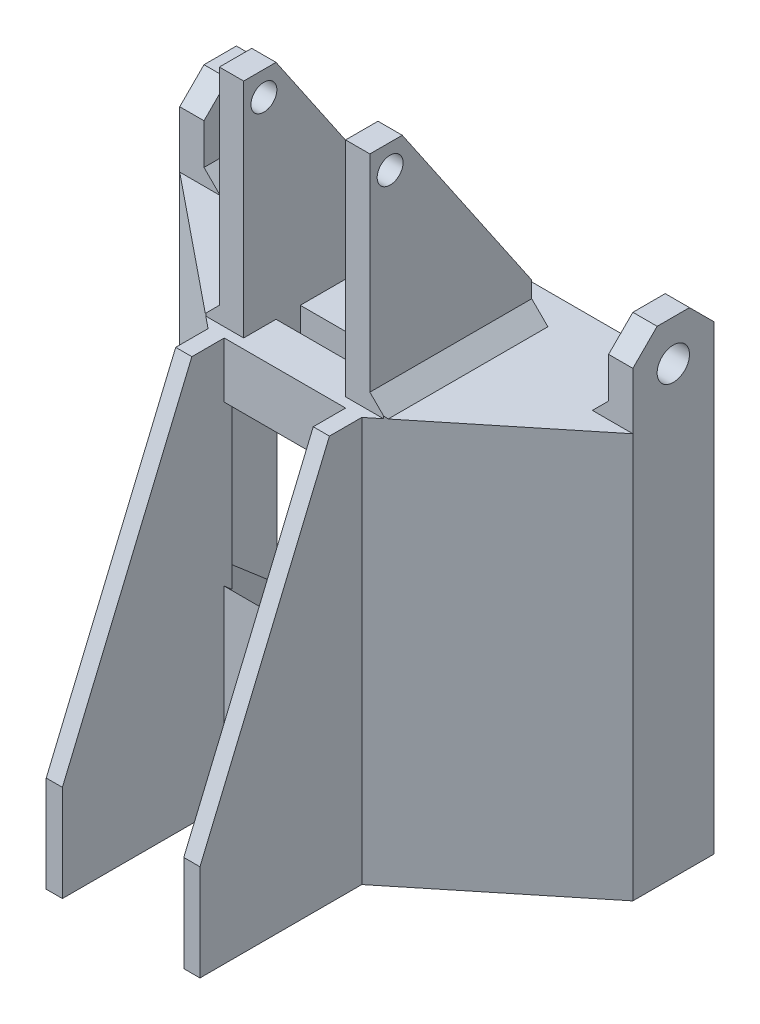
SolidWorks part; units mm, degrees
ref_plane "Alzado" through (0, 0, 0) normal (0, 0, 1) x (1, 0, 0)
ref_plane "Planta" through (0, 0, 0) normal (0, 1, 0) x (1, 0, 0)
ref_plane "Vista lateral" through (0, 0, 0) normal (1, 0, 0) x (0, 0, -1)
sketch "Croquis1" plane through (0, 0, 0) normal (0, 1, 0) x (1, 0, 0)
  line L0 (-26, 17.3913) -> (-26, 8.3445)
  line L1 (-26, 8.3445) -> (-7.5, -6.6555)
  line L2 (-7.5, -6.6555) -> (-7.5, -32.6087)
  line L3 (-7.5, -32.6087) -> (-9.5, -32.6087)
  line L4 (-9.5, -32.6087) -> (-9.5, -7.6087)
  line L5 (-9.5, -7.6087) -> (-28, 7.3913)
  line L6 (-28, 7.3913) -> (-28, 17.3913)
  line L7 (-28, 17.3913) -> (-26, 17.3913)
  line L16 (7.5, -6.6555) -> (7.5, -32.6087)
  line L17 (7.5, -32.6087) -> (9.5, -32.6087)
  line L18 (9.5, -32.6087) -> (9.5, -7.6087)
  line L19 (9.5, -7.6087) -> (28, 7.3913)
  line L20 (28, 7.3913) -> (28, 17.3913)
  line L21 (28, 17.3913) -> (26, 17.3913)
  line L22 (26, 17.3913) -> (26, 8.3445)
  line L23 (26, 8.3445) -> (7.5, -6.6555)
  line L24 (-26, 17.3913) -> (26, 17.3913) construction
  line L25 (-7.5, -32.6087) -> (7.5, -32.6087) construction
  point P10 (0, -32.6087)
  point P17 (0, 17.3913)
  dimension "D1" = 52
  dimension "D2" = 15
  dimension "D3" = 2
  dimension "D4" = 2
  dimension "D5" = 2
  dimension "D6" = 15
  dimension "D7" = 25
  dimension "D8" = 10
extrude "Saliente-Extruir1" add sketch "Croquis1" along normal blind 45
sketch "Croquis2" plane through (0, 45, 0) normal (0, 1, 0) x (1, 0, 0)
  line L0 (-9.5, -32.6087) -> (9.5, -32.6087)
  line L1 (9.5, -32.6087) -> (9.5, -7.6087)
  line L2 (9.5, -7.6087) -> (28, 7.3913)
  line L3 (28, 7.3913) -> (28, 17.3913)
  line L4 (28, 17.3913) -> (-28, 17.3913)
  line L5 (-28, 17.3913) -> (-28, 7.3913)
  line L6 (-28, 7.3913) -> (-9.5, -7.6087)
  line L7 (-9.5, -7.6087) -> (-9.5, -32.6087)
extrude "Saliente-Extruir2" add sketch "Croquis2" along normal blind 3
extrude "Saliente-Extruir3" add sketch "Croquis2<2>" against normal blind 2 from surface starting at face at (-17.75, 0, 3.6204)
sketch "Croquis2<2>" plane through (0, 45, 0) normal (0, 1, 0) x (1, 0, 0) same geometry as "Croquis2"
sketch "Croquis4" plane through (0, 48, 0) normal (0, 1, 0) x (1, 0, 0)
  line L1 (-28, 17.3913) -> (-25, 17.3913)
  line L2 (-28, 17.3913) -> (-28, 7.3913)
  line L3 (-28, 7.3913) -> (-25, 7.3913)
  line L4 (-25, 17.3913) -> (-25, 7.3913)
  line L5 (28, 17.3913) -> (25, 17.3913)
  line L6 (28, 17.3913) -> (28, 7.3913)
  line L7 (28, 7.3913) -> (25, 7.3913)
  line L8 (25, 17.3913) -> (25, 7.3913)
  dimension "D1" = 3
  dimension "D2" = 3
extrude "Saliente-Extruir4" add sketch "Croquis4" along normal blind 10
sketch "Croquis5" plane through (28, 0, 0) normal (1, 0, 0) x (0, 0, -1)
  line L0 (7.3913, 58) -> (17.3913, 58) construction
  circle A0 centre (12.3913, 53) radius 2
  dimension "D1" = 4
  dimension "D2" = 5
extrude "Cortar-Extruir1" cut sketch "Croquis5" against normal through all
chamfer "Chaflán1" distance 3 angle 45 4 edges at (-26.5, 58, -7.3913) (-26.5, 58, -17.3913) (26.5, 58, -7.3913) (26.5, 58, -17.3913)
sketch "Croquis7" plane through (9.5, 0, 0) normal (1, 0, 0) x (0, 0, -1)
  line L0 (-32.6087, -2) -> (-11.6087, 48)
  line L1 (-32.6087, 48) -> (-7.6087, 48) construction
  line L2 (-11.6087, 48) -> (-32.6087, 48)
  line L3 (-32.6087, 48) -> (-32.6087, -2)
  dimension "D1" = 4
extrude "Cortar-Extruir3" cut sketch "Croquis7" against normal through all
sketch "Croquis13" plane through (-26, 0, 0) normal (1, 0, 0) x (0, 0, -1)
  line L0 (17.3913, 45) -> (-12.8687, 45)
  line L1 (-12.8687, 45) -> (-14.9687, 40)
  line L2 (-32.6087, -2) -> (-11.6087, 48) construction
  line L3 (-14.9687, 40) -> (17.3913, 45)
  line L4 (17.3913, 0) -> (-31.7687, 0)
  line L5 (-32.6087, -2) -> (-11.6087, 48) construction
  line L6 (-31.7687, 0) -> (-18.7487, 31)
  line L7 (-18.7487, 31) -> (17.3913, 0)
  dimension "D1" = 5
  dimension "D2" = 9
extrude "Saliente-Extruir7" add sketch "Croquis13" along normal through all
sketch "Croquis6" plane through (0, -2, 0) normal (0, -1, 0) x (1, 0, 0)
  line L1 (-7.5, 27.6087) -> (7.5, 27.6087)
  line L2 (-7.5, 27.6087) -> (-7.5, 7.6087)
  line L3 (-7.5, 7.6087) -> (7.5, 7.6087)
  line L4 (7.5, 27.6087) -> (7.5, 7.6087)
  line L5 (-9.5, 32.6087) -> (-9.5, 7.6087) construction
  point P6 (0, 7.6087)
  dimension "D1" = 2
  dimension "D2" = 20
extrude "Cortar-Extruir5" cut sketch "Croquis6" against normal through all
sketch "Croquis14" plane through (0, -2, 0) normal (0, -1, 0) x (1, 0, 0)
  line L0 (-28, -7.3913) -> (-9.5, 7.6087)
  line L1 (-9.5, 7.6087) -> (-9.5, 32.6087)
  line L2 (-9.5, 32.6087) -> (-28, 32.6087)
  line L3 (-28, 32.6087) -> (-28, -7.3913)
  line L4 (28, -7.3913) -> (9.5, 7.6087)
  line L5 (9.5, 7.6087) -> (9.5, 32.6087)
  line L6 (9.5, 32.6087) -> (28, 32.6087)
  line L7 (28, 32.6087) -> (28, -7.3913)
extrude "Cortar-Extruir6" cut sketch "Croquis14" against normal through all
sketch "Croquis15" plane through (9.5, 0, 0) normal (1, 0, 0) x (0, 0, -1)
  line L0 (-27.6087, -2) -> (-27.6087, 9.9048)
  line L1 (-7.6087, -2) -> (-32.6087, -2) construction
  line L2 (-27.6087, 9.9048) -> (-32.6087, -2)
  line L3 (-32.6087, -2) -> (-27.6087, -2)
extrude "Cortar-Extruir7" cut sketch "Croquis15" against normal through all
sketch "Croquis16" plane through (0, 48, 0) normal (0, 1, 0) x (1, 0, 0)
  line L0 (7.5, -7.6087) -> (-7.5, -7.6087) construction
  line L1 (-6.3, -2.4087) -> (6.3, -2.4087)
  line L2 (-6.3, -2.4087) -> (-6.3, 0.5913)
  line L3 (-6.3, 0.5913) -> (6.3, 0.5913)
  line L4 (6.3, -2.4087) -> (6.3, 0.5913)
  line L5 (-6.3, -2.4087) -> (6.3, 0.5913) construction
  line L6 (-6.3, 0.5913) -> (6.3, -2.4087) construction
  point P0 (0, -0.9087)
  dimension "D1" = 5.2
  dimension "D2" = 3
  dimension "D3" = 12.6
extrude "Cortar-Extruir8" cut sketch "Croquis16" against normal blind 5
sketch "Croquis18" plane through (0, 48, 0) normal (0, 1, 0) x (1, 0, 0)
  line L0 (-6.3, 0.5913) -> (-6.3, 15.6495) construction
  line L1 (6.3, 0.5913) -> (6.3, 15.6495) construction
  line L3 (-6.3, -6.4087) -> (-9.3, -6.4087)
  line L4 (-6.3, -6.4087) -> (-6.3, 13.5913)
  line L5 (-6.3, 13.5913) -> (-9.3, 13.5913)
  line L6 (-9.3, -6.4087) -> (-9.3, 13.5913)
  line L7 (6.3, -6.4087) -> (9.3, -6.4087)
  line L8 (6.3, -6.4087) -> (6.3, 13.5913)
  line L9 (6.3, 13.5913) -> (9.3, 13.5913)
  line L10 (9.3, -6.4087) -> (9.3, 13.5913)
  line L11 (-6.3, 0.5913) -> (-6.3, -2.4087) construction
  line L12 (-6.3, -2.4087) -> (6.3, -2.4087) construction
  dimension "D1" = 3
  dimension "D2" = 3
  dimension "D3" = 20
  dimension "D4" = 4
extrude "Saliente-Extruir8" add sketch "Croquis18" along normal blind 27.5
sketch "Croquis19" [suppressed] plane through (0, 75.5, 0) normal (0, 1, 0) x (1, 0, 0)
  line L1 (-6.3, -6.4087) -> (6.3, -6.4087)
  line L2 (-6.3, -6.4087) -> (-6.3, -2.4087)
  line L3 (-6.3, -2.4087) -> (6.3, -2.4087)
  line L4 (6.3, -6.4087) -> (6.3, -2.4087)
sketch "Croquis20" plane through (-9.3, 0, 0) normal (-1, 0, 0) x (0, 0, 1)
  line L0 (2.4087, 75.5) -> (-13.5913, 52)
  line L1 (-13.5913, 75.5) -> (6.4087, 75.5) construction
  line L2 (-13.5913, 75.5) -> (-13.5913, 48) construction
  line L3 (-13.5913, 52) -> (-13.5913, 75.5)
  line L4 (-13.5913, 75.5) -> (2.4087, 75.5)
  line L5 (6.4087, 75.5) -> (6.4087, 48) construction
  dimension "D1" = 4
  dimension "D2" = 4
extrude "Cortar-Extruir9" cut sketch "Croquis20" against normal up to surface (18.6 mm away) up to face at (9.3, 61.75, -3.5913)
sketch "Croquis21" plane through (0, 48, 0) normal (0, 1, 0) x (1, 0, 0)
  line L1 (-2, 9.7711) -> (2, 9.7711)
  line L2 (-2, 9.7711) -> (-2, 19.7711)
  line L3 (-2, 19.7711) -> (2, 19.7711)
  line L4 (2, 9.7711) -> (2, 19.7711)
  line L5 (-2, 9.7711) -> (2, 19.7711) construction
  line L6 (-2, 19.7711) -> (2, 9.7711) construction
  point P0 (0, 14.7711)
  dimension "D1" = 4
  dimension "D2" = 10
extrude "Cortar-Extruir10" cut sketch "Croquis21" against normal blind 3
sketch "Croquis22" plane through (9.3, 0, 0) normal (1, 0, 0) x (0, 0, -1)
  line L9 (-6.4087, 75.5) -> (-6.4087, 48) construction
  circle A0 centre (-3.9087, 72.5186) radius 1.6
  dimension "D1" = 3.2
  dimension "D2" = 2.5
extrude "Cortar-Extruir11" cut sketch "Croquis22" against normal through all
chamfer "Chaflán2" distance 2 angle 45 4 edges at (25, 48, -12.3913) (-25, 48, -12.3913) (-9.3, 48, -3.5913) (9.3, 48, -3.5913)
